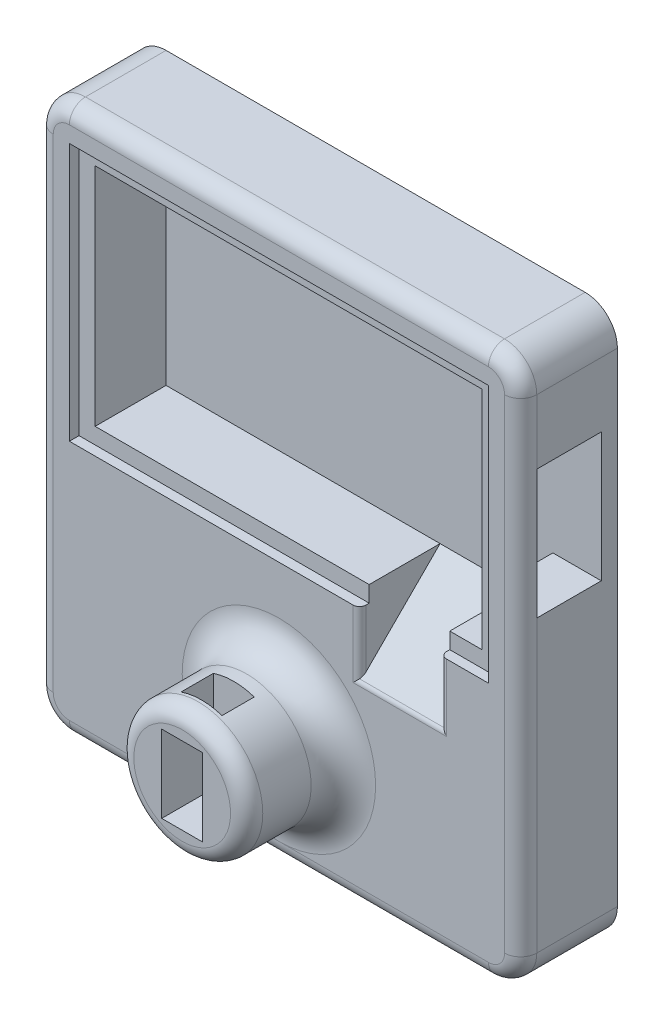
SolidWorks part; units mm, degrees
ref_plane "Přední rovina" through (0, 0, 0) normal (0, 0, 1) x (1, 0, 0)
ref_plane "Horní rovina" through (0, 0, 0) normal (0, 1, 0) x (1, 0, 0)
ref_plane "Pravá rovina" through (0, 0, 0) normal (1, 0, 0) x (0, 0, -1)
sketch "Skica1" plane through (0, 0, 0) normal (0, 0, 1) x (1, 0, 0)
  line L11 (0, 0) -> (150, 0)
  line L12 (0, 0) -> (0, 170)
  line L13 (0, 170) -> (150, 170)
  line L14 (150, 0) -> (150, 170)
  dimension "D1" = 150
  dimension "D2" = 170
extrude "Přidat vysunutím3" add sketch "Skica1" along normal blind 30
fillet "Zaoblit1" radius 10 4 edges at (150, 0, 15) (150, 170, 15) (0, 170, 15) (0, 0, 15)
sketch "Skica2" plane through (0, 0, 30) normal (0, 0, 1) x (1, 0, 0)
  line L0 (0, 160) -> (0, 10) construction
  line L1 (140, 170) -> (10, 170) construction
  circle A0 centre (75, 35) radius 20
  dimension "D1" = 40
  dimension "D2" = 75
  dimension "D3" = 135
extrude "Přidat vysunutím4" add sketch "Skica2" along normal blind 30
fillet "Zaoblit2" radius 10 1 edges at (55, 35, 30)
fillet "Zaoblit3" radius 5 1 edges at (95, 35, 60)
sketch "Skica4" plane through (0, 0, 30) normal (0, 0, 1) x (1, 0, 0)
  line L0 (0, 160) -> (0, 10) construction
  line L1 (15, 155) -> (135, 155)
  line L2 (15, 155) -> (15, 85)
  line L3 (15, 85) -> (135, 85)
  line L4 (135, 155) -> (135, 85)
  line L5 (140, 170) -> (10, 170) construction
  line L6 (150, 10) -> (150, 160) construction
  circle A0 centre (75, 35) radius 30 construction
  dimension "D1" = 15
  dimension "D2" = 15
  dimension "D3" = 15
  dimension "D4" = 50
fillet "Zaoblit5" radius 5 8 edges at (2.9289, 2.9289, 30) (0, 85, 30) (2.9289, 167.0711, 30) (75, 170, 30) (147.0711, 167.0711, 30) (150, 85, 30) (147.0711, 2.9289, 30) (75, 0, 30)
sketch "Skica9" plane through (0, 0, 60) normal (0, 0, 1) x (1, 0, 0)
  line L0 (68.65, 47) -> (81.35, 23)
  line L1 (68.65, 47) -> (81.35, 47)
  line L2 (68.65, 47) -> (68.65, 23)
  line L3 (68.65, 23) -> (81.35, 23)
  line L4 (81.35, 47) -> (81.35, 23)
  line L5 (81.35, 47) -> (68.65, 23)
  line L6 (75, 50) -> (75, 20)
  line L7 (60, 35) -> (90, 35)
  circle A0 centre (75, 35) radius 15 construction
  point P9 (75, 35)
  point P12 (75, 35)
  dimension "D1" = 24
  dimension "D2" = 12.7
extrude "Odebrat vysunutím3" cut sketch "Skica9" against normal blind 16 contours L2 L7 L0 | L6 L1 L0 | L1 L6 L5 | L5 L7 L4 | L7 L0 L4 | L0 L6 L3 | L6 L5 L3 | L7 L2 L5 region at (72.8833, 43, 60) region at (70.7667, 39, 60) region at (79.2333, 31, 60) region at (77.1167, 43, 60) region at (72.8833, 27, 60) region at (77.1167, 27, 60) region at (70.7667, 31, 60) region at (79.2333, 39, 60)
sketch "Skica10" plane through (0, 47, 0) normal (0, -1, 0) x (-1, 0, 0)
  line L0 (-68.65, -44) -> (-81.35, -44) construction
  line L1 (-68.65, -44) -> (-81.35, -44)
  line L2 (-68.65, -44) -> (-68.65, -54)
  line L3 (-68.65, -54) -> (-81.35, -54)
  line L4 (-81.35, -44) -> (-81.35, -54)
  line L5 (-81.35, -44) -> (-81.35, -60) construction
  dimension "D1" = 10
  dimension "D2" = 12.7
  dimension "D3" = 0
extrude "Odebrat vysunutím4" cut sketch "Skica10" against normal through all
extrude "Odebrat vysunutím5" cut sketch "Skica4" against normal blind 25
sketch "Skica12" plane through (0, 0, 30) normal (0, 0, 1) x (1, 0, 0)
  line L0 (15, 85) -> (135, 85) construction
  line L1 (100, 85) -> (125, 85)
  line L2 (100, 85) -> (100, 55)
  line L3 (100, 55) -> (125, 55)
  line L4 (125, 85) -> (125, 55)
  line L5 (135, 85) -> (135, 155) construction
  dimension "D1" = 25
  dimension "D2" = 30
  dimension "D3" = 10
extrude "Odebrat vysunutím6" cut sketch "Skica12" against normal blind 25
chamfer "Zkosení2" distance 30 angle 45 1 edges at (112.5, 55, 5)
fillet "Zaoblit6" radius 2 1 edges at (112.5, 60, 30)
fillet "Zaoblit7" radius 2 1 edges at (100, 72.0858, 30)
fillet "Zaoblit8" radius 2 1 edges at (125, 72.0858, 30)
sketch "Skica13" plane through (0, 0, 30) normal (0, 0, 1) x (1, 0, 0)
  line L0 (10, 160) -> (10, 80)
  line L1 (10, 80) -> (140, 80)
  line L2 (140, 80) -> (140, 160)
  line L3 (140, 160) -> (10, 160)
  line L4 (135, 155) -> (15, 155) construction
  line L5 (15, 155) -> (15, 85) construction
  line L6 (15, 85) -> (98, 85) construction
  line L7 (135, 85) -> (135, 155) construction
  dimension "D1" = 5
  dimension "D2" = 5
  dimension "D3" = 5
  dimension "D4" = 5
extrude "Odebrat vysunutím7" cut sketch "Skica13" against normal blind 3
sketch "Skica14" plane through (135, 0, 0) normal (-1, 0, 0) x (0, 0, 1)
  line L0 (5, 85) -> (5, 155) construction
  line L1 (5, 140) -> (25, 140)
  line L2 (5, 140) -> (5, 100)
  line L3 (5, 100) -> (25, 100)
  line L4 (25, 140) -> (25, 100)
  line L6 (5, 155) -> (27, 155) construction
  dimension "D1" = 20
  dimension "D2" = 40
  dimension "D3" = 15
extrude "Odebrat vysunutím8" cut sketch "Skica14" against normal blind 50
